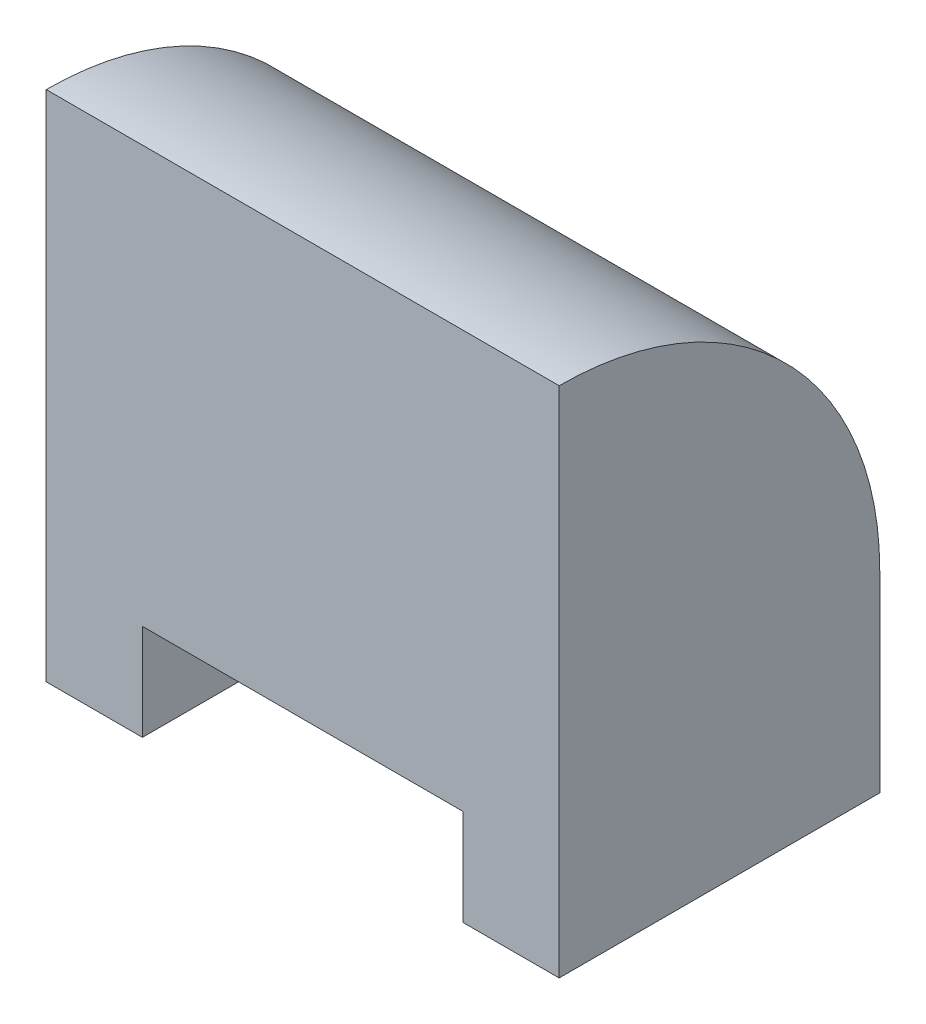
SolidWorks part; units mm, degrees
ref_plane "Front Plane" through (0, 0, 0) normal (0, 0, 1) x (1, 0, 0)
ref_plane "Top Plane" through (0, 0, 0) normal (0, 1, 0) x (1, 0, 0)
ref_plane "Right Plane" through (0, 0, 0) normal (1, 0, 0) x (0, 0, -1)
sketch "Sketch1" plane through (0, 0, 0) normal (1, 0, 0) x (0, 0, -1)
  line L0 (0, 0) -> (50, 0)
  line L1 (50, 0) -> (50, 80)
  line L2 (50, 80) -> (0, 80)
  line L3 (0, 80) -> (0, 0)
  dimension "D1" = 80
  dimension "D3" = 50
extrude "Boss-Extrude1" add sketch "Sketch1" along normal blind 80 contours L3 L0 L1 L2
sketch "Sketch4" plane through (0, 0, 0) normal (0, 0, 1) x (1, 0, 0)
  line L0 (15, 0) -> (15, 15)
  line L1 (80, 0) -> (0, 0) construction
  line L2 (15, 15) -> (65, 15)
  line L3 (65, 15) -> (65, 0)
  line L4 (65, 0) -> (15, 0)
  line L5 (0, 80) -> (0, 0) construction
  line L6 (80, 80) -> (80, 0) construction
  dimension "D1" = 15
  dimension "D2" = 15
  dimension "D3" = 15
extrude "Cut-Extrude2" cut sketch "Sketch4" against normal through all
fillet "Fillet1" radius 50 1 edges at (40, 80, -50)
sketch "Sketch5" plane through (0, 15, 0) normal (0, -1, 0) x (1, 0, 0)
  line L0 (80, 0) -> (80, -50) construction
  line L1 (65, 0) -> (15, 0) construction
  circle A0 centre (40, -25) radius 5
  dimension "D1" = 40
  dimension "D2" = 25
extrude "Cut-Extrude3" cut sketch "Sketch5" against normal blind 25
